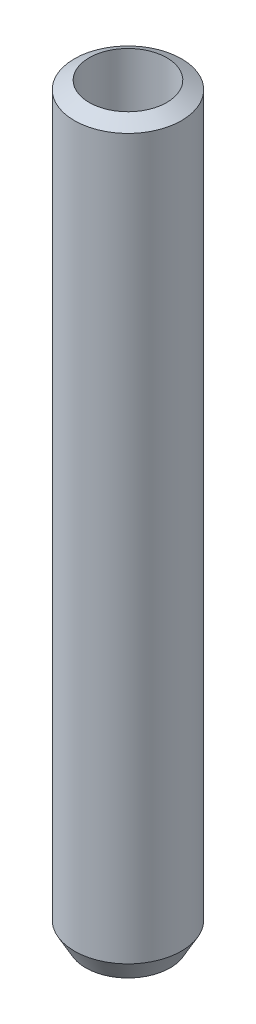
SolidWorks part; units mm, degrees
ref_plane "Front Plane" through (0, 0, 0) normal (0, 0, 1) x (1, 0, 0)
ref_plane "Top Plane" through (0, 0, 0) normal (0, 1, 0) x (1, 0, 0)
ref_plane "Right Plane" through (0, 0, 0) normal (1, 0, 0) x (0, 0, -1)
sketch "Sketch1" plane through (0, 0, 0) normal (0, 1, 0) x (1, 0, 0)
  circle A0 centre (0, 0) radius 25
  dimension "SHAFT_OD" = 50
extrude "Boss-Extrude1" add sketch "Sketch1" along normal blind 350.3169
sketch "Sketch2" plane through (0, 0, 0) normal (0, 1, 0) x (1, 0, 0)
  circle A0 centre (0, 0) radius 18.1041
  dimension "BORE_D" = 36.2082
extrude "Cut-Extrude1" cut sketch "Sketch2" along normal through all
chamfer "Chamfer1" distance 5.2963 angle 60.743 2 edges at (0, 350.3169, 25) (0, 0, 25) first distance on face at (0, 350.3169, 25) first distance on face at (0, 0, 18.1041)
